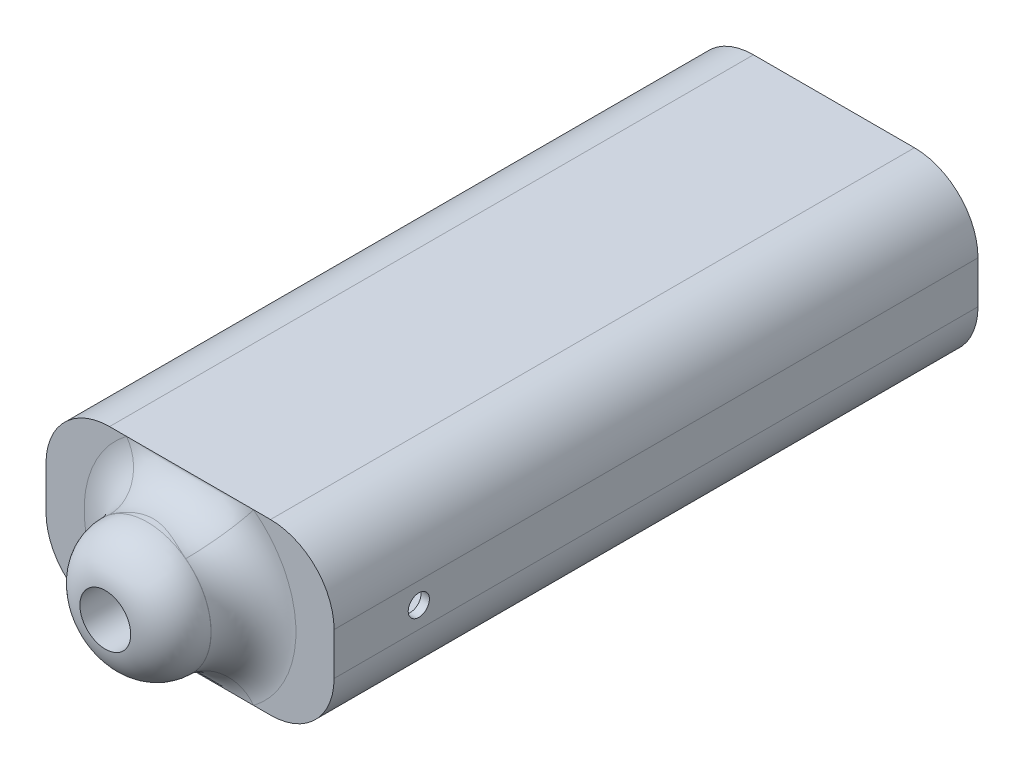
SolidWorks part; units mm, degrees
ref_plane "Front Plane" through (0, 0, 0) normal (0, 0, 1) x (1, 0, 0)
ref_plane "Top Plane" through (0, 0, 0) normal (0, 1, 0) x (1, 0, 0)
ref_plane "Right Plane" through (0, 0, 0) normal (1, 0, 0) x (0, 0, -1)
sketch "Sketch1" plane through (0, 0, 0) normal (0, 0, 1) x (1, 0, 0)
  line L1 (-17, 10) -> (17, 10)
  line L2 (-17, 10) -> (-17, -10)
  line L3 (-17, -10) -> (17, -10)
  line L4 (17, 10) -> (17, -10)
  line L5 (-17, 10) -> (17, -10) construction
  line L6 (-17, -10) -> (17, 10) construction
  circle A0 centre (0, 0) radius 2
  point P0 (0, 0)
  dimension "D3" = 4
  dimension "D1" = 20
  dimension "D2" = 34
extrude "Boss-Extrude1" add sketch "Sketch1" against normal blind 1
sketch "Sketch2" plane through (0, 0, -1) normal (0, 0, -1) x (-1, 0, 0)
  line L0 (-17, 10) -> (-17, -10)
  line L1 (17, -10) -> (-17, -10) construction
  line L2 (-17, -10) -> (17, -10)
  line L3 (17, -10) -> (17, 10)
  line L4 (17, 10) -> (-17, 10)
  line L5 (16, 9) -> (-16, 9)
  line L6 (-16, 9) -> (-16, -9)
  line L7 (-16, -9) -> (16, -9)
  line L8 (16, -9) -> (16, 9)
  dimension "D1" = 1
extrude "Boss-Extrude2" add sketch "Sketch2" along normal blind 75
fillet "Fillet2" radius 7.5 8 edges at (17, 10, -38) (17, -10, -38) (-17, -10, -38) (-17, 10, -38) (-16, -9, -38.5) (-16, 9, -38.5) (16, 9, -38.5) (16, -9, -38.5)
sketch "Sketch4" plane through (0, 0, 0) normal (0, 0, 1) x (1, 0, 0)
  circle A0 centre (0, 0) radius 7.5
  circle A1 centre (0, 0) radius 3
  dimension "D1" = 6
  dimension "D2" = 15
extrude "Boss-Extrude3" add sketch "Sketch4" along normal blind 10
fillet "Fillet3" radius 5 2 edges at (7.5, 0, 0) (7.5, 0, 10)
sketch "Sketch5" plane through (17, 0, 0) normal (1, 0, 0) x (0, 0, -1)
  circle A0 centre (10, 0) radius 1.25
  point P2 (0, 0)
  point P4 (0, 0)
  dimension "D1" = 2.5
  dimension "D2" = 10
extrude "Cut-Extrude1" cut sketch "Sketch5" against normal through all
